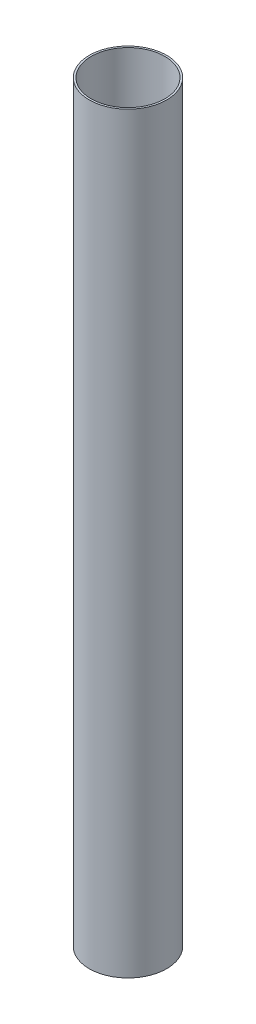
SolidWorks part; units mm, degrees
ref_plane "Front Plane" through (0, 0, 0) normal (0, 0, 1) x (1, 0, 0)
ref_plane "Top Plane" through (0, 0, 0) normal (0, 1, 0) x (1, 0, 0)
ref_plane "Right Plane" through (0, 0, 0) normal (1, 0, 0) x (0, 0, -1)
sketch "Sketch1" plane through (0, 0, 0) normal (0, 1, 0) x (1, 0, 0)
  circle A0 centre (0, 0) radius 41.15
  circle A1 centre (0, 0) radius 39.15
  dimension "D1" = 82.3
  dimension "D2" = 78.3
extrude "Boss-Extrude1" add sketch "Sketch1" along normal blind 800
